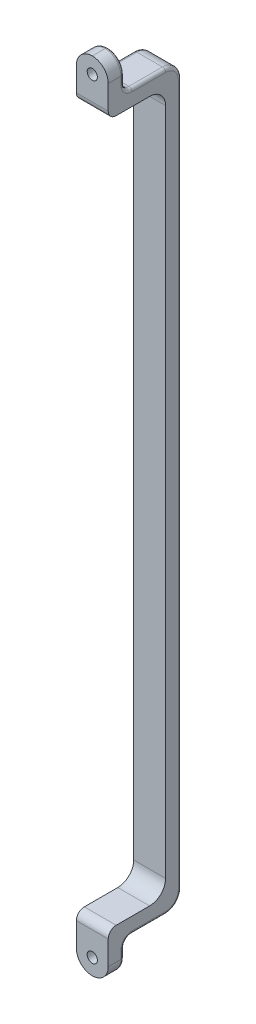
SolidWorks part; units mm, degrees
ref_plane "Front Plane" through (0, 0, 0) normal (0, 0, 1) x (1, 0, 0)
ref_plane "Top Plane" through (0, 0, 0) normal (0, 1, 0) x (1, 0, 0)
ref_plane "Right Plane" through (0, 0, 0) normal (1, 0, 0) x (0, 0, -1)
sketch "Sketch1" plane through (0, 0, 0) normal (0, 0, 1) x (1, 0, 0)
  line L0 (0, 0) -> (0, 230)
  line L1 (0, 230) -> (10, 230)
  line L2 (10, 230) -> (10, 0)
  line L3 (10, 0) -> (0, 0)
  dimension "D1" = 230
  dimension "D2" = 10
extrude "Boss-Extrude1" add sketch "Sketch1" along normal blind 5
sketch "Sketch2" plane through (0, 0, 5) normal (0, 0, 1) x (1, 0, 0)
  line L0 (0, 0) -> (10, 0)
  line L1 (10, 0) -> (10, 5)
  line L2 (10, 0) -> (10, 230) construction
  line L3 (10, 5) -> (0, 5)
  line L4 (0, 230) -> (0, 0) construction
  line L5 (0, 5) -> (0, 0)
  line L6 (0, 230) -> (10, 230)
  line L7 (10, 230) -> (10, 225)
  line L8 (10, 225) -> (0, 225)
  line L9 (0, 225) -> (0, 230)
  dimension "D1" = 5
  dimension "D2" = 5
extrude "Boss-Extrude2" add sketch "Sketch2" along normal blind 18
sketch "Sketch3" plane through (0, 0, 23) normal (0, 0, 1) x (1, 0, 0)
  line L0 (0, 230) -> (10, 230)
  line L1 (10, 230) -> (10, 240)
  line L2 (10, 240) -> (0, 240)
  line L3 (0, 240) -> (0, 230)
  line L4 (0, 0) -> (10, 0)
  line L5 (10, 0) -> (10, -10)
  line L6 (10, -10) -> (0, -10)
  line L7 (0, -10) -> (0, 0)
  dimension "D1" = 10
  dimension "D2" = 10
extrude "Boss-Extrude3" add sketch "Sketch3" against normal blind 5
sketch "Sketch4" plane through (0, 0, 18) normal (0, 0, -1) x (-1, 0, 0)
  line L0 (0, 0) -> (0, -10) construction
  line L1 (0, -10) -> (-10, -10) construction
  line L2 (-10, 240) -> (0, 240) construction
  line L3 (0, 240) -> (0, 230) construction
  circle A0 centre (-5, -5) radius 1.6
  circle A1 centre (-5, 235) radius 1.6
  dimension "D1" = 3.2
  dimension "D2" = 3.2
  dimension "D3" = 5
  dimension "D4" = 5
  dimension "D5" = 5
  dimension "D6" = 5
extrude "Cut-Extrude1" cut sketch "Sketch4" against normal through all
sketch "Sketch5" plane through (0, 0, 18) normal (0, 0, -1) x (-1, 0, 0)
  circle A0 centre (-5, -5) radius 2.5
  circle A1 centre (-5, 235) radius 2.5
  dimension "D1" = 5
  dimension "D2" = 5
extrude "Cut-Extrude2" cut sketch "Sketch5" against normal blind 1.5
fillet "Fillet1" radius 5 8 edges at (0, -10, 20.5) (10, -10, 20.5) (0, 240, 20.5) (10, 240, 20.5) (5, 225, 5) (5, 230, 0) (5, 5, 5) (5, 0, 0)
fillet "Fillet2" radius 2.5 4 edges at (5, 225, 23) (5, 230, 18) (5, 5, 23) (5, 0, 18)
fillet "Fillet3" radius 1 22 edges at (1.4645, 238.5355, 18) (0, 233.75, 18) (0, 230.7322, 17.2678) (0, 230, 10.25) (0, 228.5355, 1.4645) (0, 115, 0) (0, 1.4645, 1.4645) (0, 0, 10.25) (0, -0.7322, 17.2678) (0, -3.75, 18) (1.4645, -8.5355, 18) (8.5355, -8.5355, 18) (10, -3.75, 18) (10, -0.7322, 17.2678) (10, 0, 10.25) (10, 1.4645, 1.4645) (10, 115, 0) (10, 228.5355, 1.4645) (10, 230, 10.25) (10, 230.7322, 17.2678) (10, 233.75, 18) (8.5355, 238.5355, 18)
